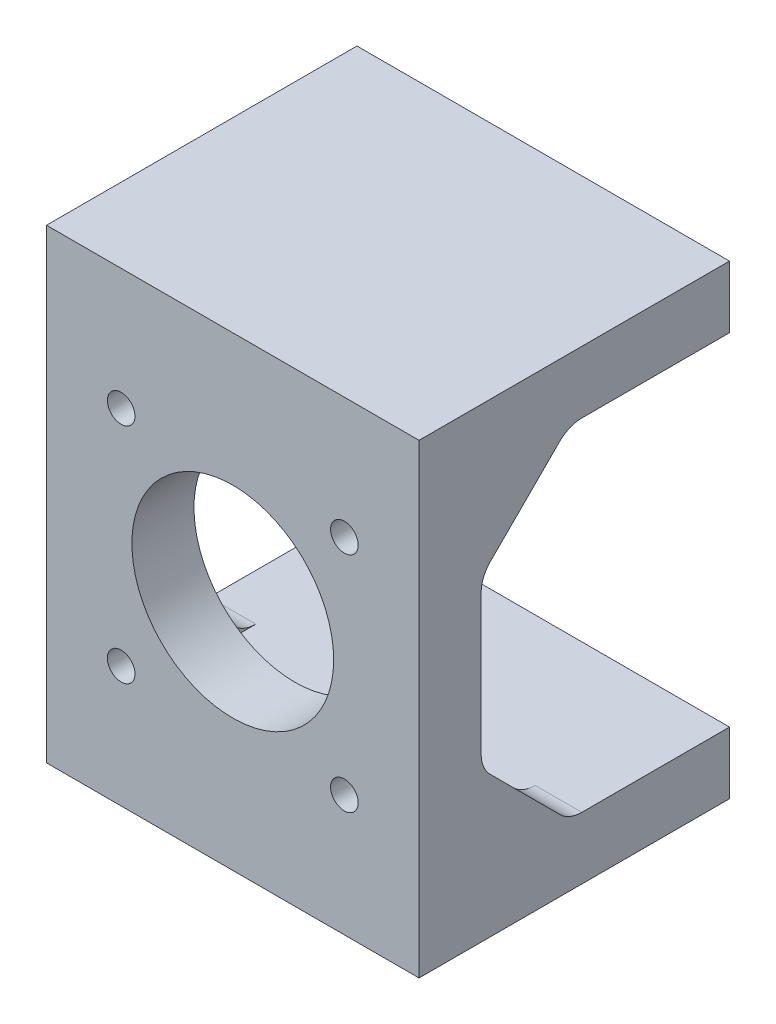
SolidWorks part; units mm, degrees
material "ABS"
ref_plane "Front Plane" through (0, 0, 0) normal (0, 0, 1) x (1, 0, 0)
ref_plane "Top Plane" through (0, 0, 0) normal (0, 1, 0) x (1, 0, 0)
ref_plane "Right Plane" through (0, 0, 0) normal (1, 0, 0) x (0, 0, -1)
sketch "Sketch1" plane through (0, 0, 0) normal (0, 0, 1) x (1, 0, 0)
  line L1 (-15.24, -19.05) -> (15.24, -19.05)
  line L2 (-15.24, -19.05) -> (-15.24, 19.05)
  line L3 (-15.24, 19.05) -> (15.24, 19.05)
  line L4 (15.24, -19.05) -> (15.24, 19.05)
  line L5 (-15.24, -19.05) -> (15.24, 19.05) construction
  line L6 (-15.24, 19.05) -> (15.24, -19.05) construction
  circle A0 centre (0, 0) radius 8.255
  point P0 (0, 0)
  dimension "D3" = 16.51
  dimension "D1" = 38.1
  dimension "D2" = 30.48
extrude "Boss-Extrude with 4-40 Tap Drill Holes" add sketch "Sketch1" against normal mid plane 25.4
hole_wizard "#4-40 Tapped Hole1" positions "Sketch7" profile "Sketch8" tap size "#4-40" standard "ANSI Inch" end condition up to next
sketch "Sketch7" plane through (0, 0, 12.7) normal (0, 0, 1) x (1, 0, 0)
  line L9 (-9.1313, 9.1313) -> (9.1313, 9.1313) construction
  line L10 (-9.1313, 9.1313) -> (-9.1313, -9.1313) construction
  line L11 (-9.1313, -9.1313) -> (9.1313, -9.1313) construction
  line L12 (9.1313, 9.1313) -> (9.1313, -9.1313) construction
  point P212 (-9.1313, 9.1313)
  point P213 (9.1313, -9.1313)
  point P216 (-9.1313, -9.1313)
  point P217 (9.1313, 9.1313)
  point P289 (9.1313, 0)
  point P293 (0, -9.1313)
  dimension "D1" = 18.2626
  dimension "D2" = 18.2626
sketch "Sketch8" plane through (-9.1313, 9.1313, 12.7) normal (1, 0, 0) x (0, -1, 0)
  line L0 (0, 0) -> (0, 25.4)
  line L1 (0, 25.4) -> (1.1303, 25.4)
  line L2 (1.1303, 25.4) -> (1.1303, 0)
  line L5 (1.1303, 0) -> (0, 0)
  line L11 (0, -6.35) -> (0, 107.95) construction
  dimension "Thru Tap Drill Dia." = 2.2606
  dimension "Thru Tap Drill Depth" = 25.4
cosmetic thread "Hole Thread1" parameters "D2"=2.8448
cosmetic thread "Hole Thread2" parameters "D2"=2.8448
cosmetic thread "Hole Thread3" parameters "D2"=2.8448
cosmetic thread "Hole Thread4" parameters "D2"=2.8448
sketch "Sketch3" plane through (15.24, 0, 0) normal (1, 0, 0) x (0, 0, -1)
  line L0 (12.7, -19.05) -> (12.7, 19.05) construction
  line L1 (12.7, 13.97) -> (-7.62, 13.97)
  line L2 (12.7, 13.97) -> (12.7, -13.97)
  line L3 (12.7, -13.97) -> (-7.62, -13.97)
  line L4 (-7.62, 13.97) -> (-7.62, -13.97)
  line L5 (12.7, 19.05) -> (-12.7, 19.05) construction
  line L6 (12.7, -19.05) -> (-12.7, -19.05) construction
  line L7 (-12.7, -19.05) -> (-12.7, 19.05) construction
  dimension "D1" = 5.08
  dimension "D2" = 5.08
  dimension "D3" = 5.08
extrude "Cut-Extrude1" cut sketch "Sketch3" against normal up to next
fillet "Fillet1" radius 2.54 2 edges at (0, -13.97, 7.62) (0, 13.97, 7.62)
sketch "Sketch5" plane through (0, 19.05, 0) normal (0, 1, 0) x (1, 0, 0)
  line L4 (-15.24, 12.7) -> (-15.24, -5.08)
  line L5 (-15.24, 12.7) -> (-15.24, -5.08)
  line L6 (15.24, -5.08) -> (15.24, 12.7)
  line L7 (15.24, 12.7) -> (-15.24, 12.7)
  line L8 (-15.24, -5.08) -> (15.24, -5.08)
  line L9 (-15.24, -5.08) -> (15.24, -5.08)
  line L10 (15.24, -5.08) -> (15.24, 12.7)
  line L11 (15.24, 12.7) -> (-15.24, 12.7)
  circle A0 centre (-6.35, 7.62) radius 1.65
  circle A1 centre (6.35, 7.62) radius 1.65
  circle A2 centre (6.35, -4.445) radius 1.65
  circle A3 centre (-6.35, -4.445) radius 1.65
  dimension "D2" = 3.3
  dimension "D3" = 8.89
  dimension "D4" = 8.89
  dimension "D5" = 5.08
  dimension "D1" = 0
extrude "Clearance Holes for M3 Screw" [suppressed] cut sketch "Sketch5" against normal through all contours A0 | A3 | A2 | A1
sketch "Sketch6" plane through (15.24, 0, 0) normal (1, 0, 0) x (0, 0, -1)
  line L0 (-7.62, -6.7858) -> (-0.4358, -13.97)
  line L1 (-7.62, 11.43) -> (-7.62, -11.43) construction
  line L2 (-5.08, -13.97) -> (12.7, -13.97) construction
  line L3 (0, 0) -> (-12.7, 0) construction
  line L4 (-12.7, -19.05) -> (-12.7, 19.05) construction
  line L6 (-5.08, 13.97) -> (-0.4358, 13.97)
  line L7 (-5.08, -13.97) -> (-0.4358, -13.97)
  line L8 (-7.62, -6.7858) -> (-7.62, -11.43)
  line L9 (-7.62, 6.7858) -> (-0.4358, 13.97)
  line L10 (-7.62, 6.7858) -> (-7.62, 11.43)
  arc A1 (-7.62, -11.43) -> (-5.08, -13.97) centre (-5.08, -11.43) ccw construction
  arc A2 (-7.62, 11.43) -> (-5.08, 13.97) centre (-5.08, 11.43) cw
  arc A3 (-7.62, -11.43) -> (-5.08, -13.97) centre (-5.08, -11.43) ccw
  dimension "D1" = 45
  dimension "D2" = 10.16
extrude "Boss-Extrude1" add sketch "Sketch6" against normal blind 3.81
mirror "Mirror1" about plane through (0, 0, 0) normal (1, 0, 0) of "Boss-Extrude1"
fillet "Fillet2" radius 2.54 8 edges at (-13.335, 13.97, 0.4358) (-13.335, 6.7858, 7.62) (-13.335, -13.97, 0.4358) (-13.335, -6.7858, 7.62) (13.335, -13.97, 0.4358) (13.335, -6.7858, 7.62) (13.335, 13.97, 0.4358) (13.335, 6.7858, 7.62)
